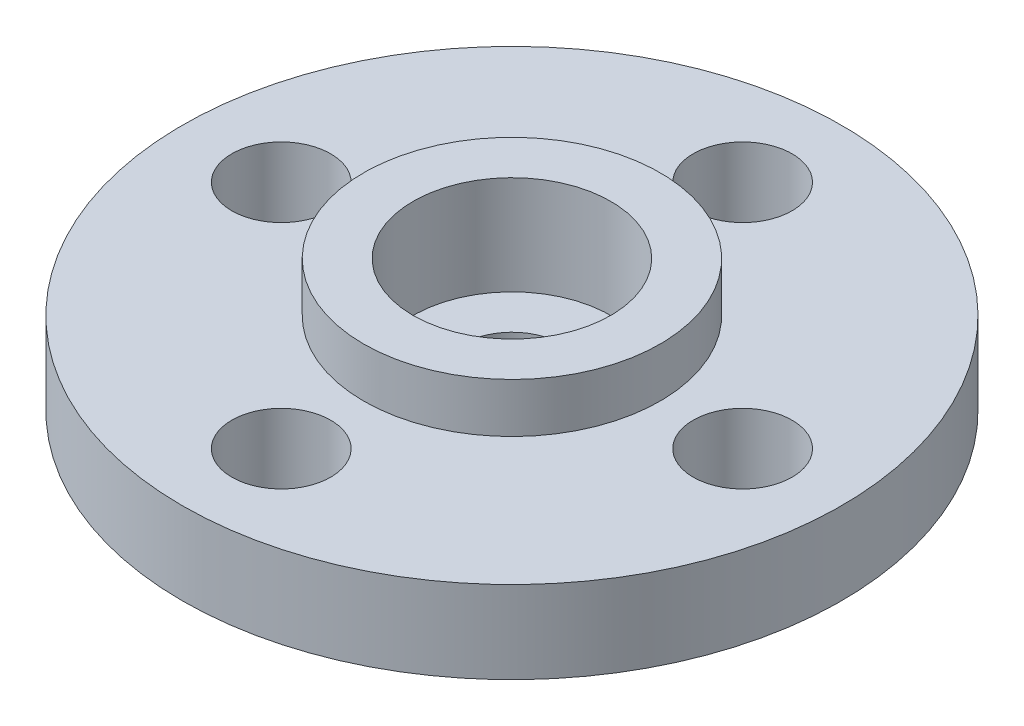
SolidWorks part; units mm, degrees
other "标注1"
sketch "草图4" plane through (10, 4, 10) normal (0.5652, 0.7256, 0.3925) x (-0.7853, 0.6189, -0.0132)
material "AISI 304"
ref_plane "前视基准面" through (0, 0, 0) normal (0, 0, 1) x (1, 0, 0)
ref_plane "上视基准面" through (0, 0, 0) normal (0, 1, 0) x (1, 0, 0)
ref_plane "右视基准面" through (0, 0, 0) normal (1, 0, 0) x (0, 0, -1)
sketch "草图1" plane through (0, 0, 0) normal (0, 1, 0) x (1, 0, 0)
  line L0 (0, 15.8996) -> (0, -14.3213) construction
  circle A0 centre (0, 0) radius 10
  circle A1 centre (0, 0) radius 1.5
  circle A2 centre (0, 7) radius 1.5
  circle A3 centre (7, 0) radius 1.5
  circle A4 centre (0, -7) radius 1.5
  circle A5 centre (-7, 0) radius 1.5
  dimension "D1" = 20
  dimension "D2" = 3
  dimension "D3" = 7
  dimension "D4" = 3
  dimension "D5" = 4
extrude "凸台-拉伸1" add sketch "草图1" along normal blind 2.5
sketch "草图2" plane through (0, 2.5, 0) normal (0, 1, 0) x (1, 0, 0)
  circle A0 centre (0, 0) radius 4.5
  circle A1 centre (0, 0) radius 3
  dimension "D1" = 9
  dimension "D2" = 6
extrude "凸台-拉伸2" add sketch "草图2" along normal blind 1.5
sketch "草图3" plane through (0, 2.5, 0) normal (0, 1, 0) x (1, 0, 0)
  circle A0 centre (0, 0) radius 3
  dimension "D1" = 6
extrude "切除-拉伸1" cut sketch "草图3" against normal blind 1.5
